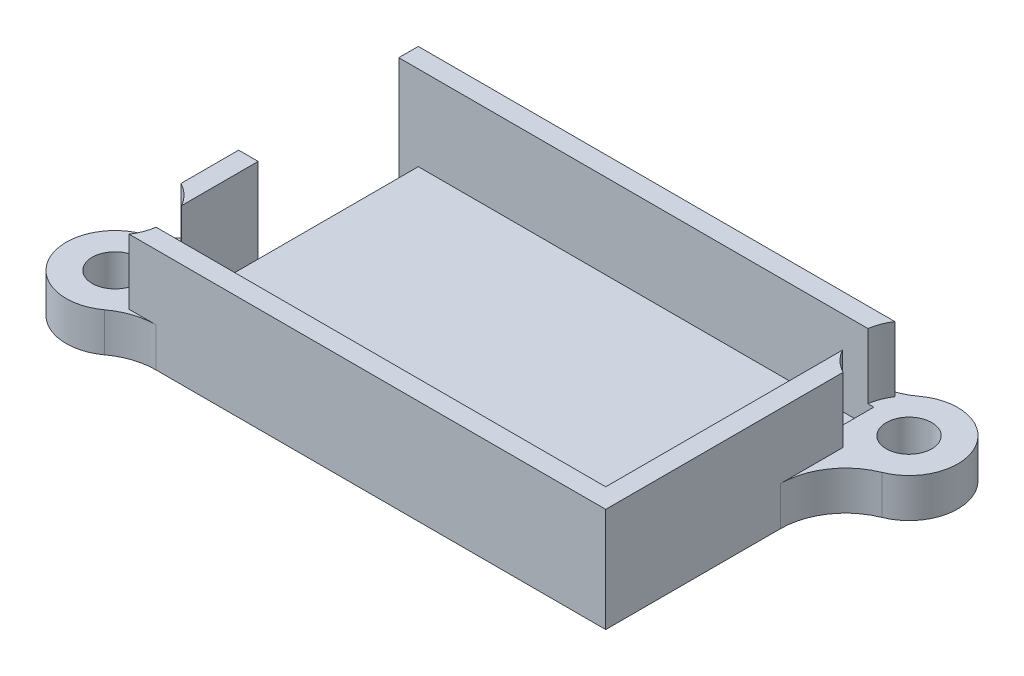
SolidWorks part; units mm, degrees
ref_plane "Front Plane" through (0, 0, 0) normal (0, 0, 1) x (1, 0, 0)
ref_plane "Top Plane" through (0, 0, 0) normal (0, 1, 0) x (1, 0, 0)
ref_plane "Right Plane" through (0, 0, 0) normal (1, 0, 0) x (0, 0, -1)
sketch "Sketch1" plane through (0, 0, 0) normal (0, 1, 0) x (1, 0, 0)
  line L0 (-19, -11.8) -> (-19, 11.8)
  line L5 (-19, 11.8) -> (19, 11.8)
  line L6 (19, -11.8) -> (19, 11.8)
  line L7 (-17.5, -10.3) -> (17.5, -10.3)
  line L8 (-17.5, -10.3) -> (-17.5, 10.3)
  line L9 (-17.5, 10.3) -> (17.5, 10.3)
  line L10 (17.5, -10.3) -> (17.5, 10.3)
  line L11 (-17.5, -10.3) -> (17.5, 10.3) construction
  line L12 (-17.5, 10.3) -> (17.5, -10.3) construction
  line L13 (-19, -11.8) -> (19, -11.8)
  line L14 (-20.75, -9.75) -> (20.75, 9.75) construction
  line L16 (-19, 10.3) -> (-17.5, 10.3)
  line L17 (-19, 10.3) -> (-19, -2)
  line L18 (-19, -2) -> (-17.5, -2)
  line L19 (-17.5, 10.3) -> (-17.5, -2)
  line L20 (-19, 10.3) -> (-17.5, -2) construction
  line L21 (-19, -2) -> (-17.5, 10.3) construction
  circle A0 centre (20.75, 9.75) radius 1.75
  circle A1 centre (-20.75, -9.75) radius 1.75
  circle A2 centre (20.75, 9.75) radius 3.75
  arc A3 (-19, -6.4334) -> (-17.6099, -11.8) centre (-20.75, -9.75) ccw
  circle A4 centre (-20.75, -9.75) radius 3.75
  point P5 (0, 0)
  point P6 (0, 0)
  point P17 (0, 0)
  point P20 (-18.25, 4.15)
  point P25 (0, 0)
  dimension "D4" = 3.5
  dimension "D5" = 2
  dimension "D7" = 19.5
  dimension "D1" = 20.6
  dimension "D2" = 35
  dimension "D6" = 2
  dimension "D3" = 1.5
extrude "Boss-Extrude1" add sketch "Sketch1" along normal blind 1.5 contours L7 L10 L9 L8 | L7 A4 L8 | L9 A2 L10 region at (0, 0, 0) region at (-17.2863, 0, 9.3329) region at (17.2863, 0, -9.3329)
extrude "Boss-Extrude2" add sketch "Sketch1<3>" along normal blind 8 contours A2 L5 L0 L16 L9 | L5 A2 L9 L10 L6 | L6 A2 L5 A0 | A4 L13 L6 A2 L10 L7 | A4 L8 L18 L0 | L13 A4 L7 L8 L0 | L0 A3 L13 A1 region at (-18.305, 0, 11.9018) region at (-18.2412, 0, 9.4563) region at (-16.8555, 0, 11.2283) region at (-18.2151, 0, 4.5262) region at (18.2412, 0, -9.4563) region at (19.1018, 0, -8.0917) region at (-0.868, 0, -11.0519)
sketch "Sketch1<3>" plane through (0, 0, 0) normal (0, 1, 0) x (1, 0, 0) same geometry as "Sketch1"
extrude "Cut-Extrude1" cut sketch "Sketch1<5>" along normal through all from offset 3 contours L0 A3 L13 A1 | L13 A4 L7 L8 L0 | L6 A2 L5 A0 | L5 A2 L9 L10 L6 region at (-18.305, 0, 11.9018) region at (-18.2412, 0, 9.4563) region at (18.2412, 0, -9.4563) region at (19.1018, 0, -8.0917)
sketch "Sketch1<5>" plane through (0, 0, 0) normal (0, 1, 0) x (1, 0, 0) same geometry as "Sketch1"
fillet "Fillet1" radius 5 4 edges at (-19, 1.5, 6.4334) (-17.6099, 1.5, 11.8) (17.6099, 1.5, -11.8) (19, 1.5, -6.4334)
